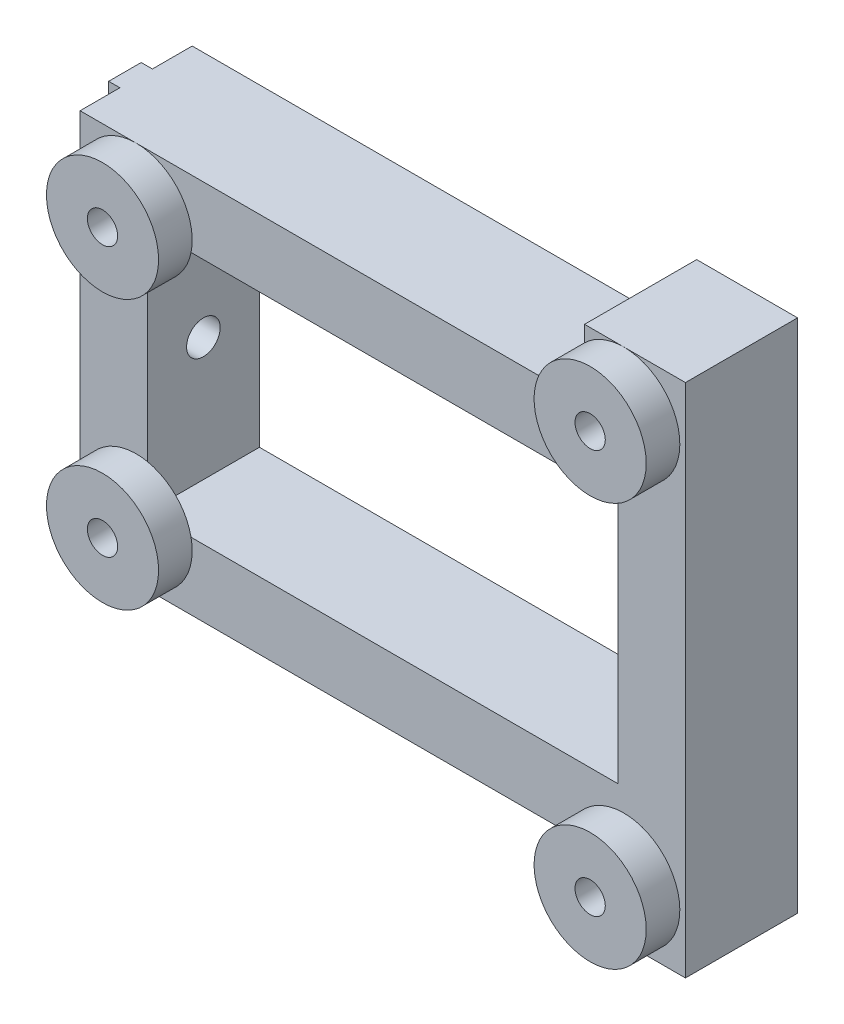
SolidWorks part; units mm, degrees
ref_plane "Plan de face" through (0, 0, 0) normal (0, 0, 1) x (1, 0, 0)
ref_plane "Plan de dessus" through (0, 0, 0) normal (0, 1, 0) x (1, 0, 0)
ref_plane "Plan de droite" through (0, 0, 0) normal (1, 0, 0) x (0, 0, -1)
sketch "Esquisse1" plane through (0, 0, 0) normal (0, 0, 1) x (1, 0, 0)
  line L1 (-27, -23) -> (27, -23)
  line L2 (-27, -23) -> (-27, 23)
  line L3 (-27, 23) -> (27, 23)
  line L4 (27, -23) -> (27, 23)
  point P7 (0, -23)
  point P8 (-27, 0)
  dimension "D1" = 46
  dimension "D2" = 54
extrude "Boss.-Extru.1" add sketch "Esquisse1" along normal blind 10
sketch "Esquisse2" plane through (0, 0, 10) normal (0, 0, 1) x (1, 0, 0)
  line L1 (-27, -23) -> (27, -23) construction
  line L2 (27, 23) -> (-27, 23) construction
  line L3 (-27, 23) -> (-27, -23) construction
  circle A0 centre (-22, -12) radius 1.35
  circle A1 centre (-22, 12) radius 1.35
  circle A2 centre (21.5, 18) radius 1.35
  circle A3 centre (21.5, -18) radius 1.35
  dimension "D1" = 2.7
  dimension "D2" = 48.5
  dimension "D3" = 5
  dimension "D4" = 11
  dimension "D5" = 11
  dimension "D6" = 5
  dimension "D7" = 5
  dimension "D8" = 24
  dimension "D9" = 36
extrude "Enlèv. mat.-Extru.1" cut sketch "Esquisse2" against normal through all
sketch "Esquisse3" plane through (0, 0, 10) normal (0, 0, 1) x (1, 0, 0)
  circle A0 centre (-22, 12) radius 5
  circle A1 centre (-22, -12) radius 5
  circle A2 centre (21.5, -18) radius 5
  circle A3 centre (21.5, 18) radius 5
  circle A4 centre (21.5, 18) radius 1.35 construction
  circle A5 centre (-22, 12) radius 1.35 construction
  circle A6 centre (-22, -12) radius 1.35 construction
  circle A7 centre (21.5, -18) radius 1.35 construction
  dimension "D1" = 10
extrude "Boss.-Extru.2" add sketch "Esquisse3" along normal blind 3
sketch "Esquisse4" plane through (0, -23, 0) normal (0, -1, 0) x (1, 0, 0)
  line L0 (-27, 10) -> (21.5, 10) construction
  line L1 (18, 10) -> (-27, 10)
  line L2 (18, 10) -> (18, 0)
  line L3 (18, 0) -> (-27, 0)
  line L4 (-27, 10) -> (-27, 0)
  dimension "D2" = 45
extrude "Enlèv. mat.-Extru.2" cut sketch "Esquisse4" against normal blind 6
sketch "Esquisse6" plane through (0, 23, 0) normal (0, 1, 0) x (1, 0, 0)
  line L0 (21.5, -10) -> (-27, -10) construction
  line L1 (-27, 0) -> (18, 0)
  line L2 (-27, 0) -> (-27, -10)
  line L3 (-27, -10) -> (18, -10)
  line L4 (18, 0) -> (18, -10)
  line L5 (-27, -10) -> (-27, 0) construction
  line L6 (27, 0) -> (-27, 0) construction
  line L7 (16.5, -10) -> (26.5, -10) construction
extrude "Enlèv. mat.-Extru.3" cut sketch "Esquisse6" against normal blind 6
sketch "Esquisse7" plane through (-27, 0, 0) normal (-1, 0, 0) x (0, 0, 1)
  line L1 (3.55, 17) -> (6.45, 17)
  line L2 (3.55, 17) -> (3.55, -17)
  line L3 (3.55, -17) -> (6.45, -17)
  line L4 (6.45, 17) -> (6.45, -17)
  line L9 (0, 17) -> (10, 17) construction
  line L10 (10, -17) -> (0, -17) construction
  point P4 (5, 17)
  point P10 (5, 17)
  dimension "D1" = 2.9
extrude "Boss.-Extru.3" add sketch "Esquisse7" along normal blind 1
sketch "Esquisse10" plane through (0, 0, 10) normal (0, 0, 1) x (1, 0, 0)
  line L0 (18, 17) -> (54.5, 17) construction
  line L1 (-21, 11) -> (21, 11)
  line L2 (-21, 11) -> (-21, -11)
  line L3 (-21, -11) -> (21, -11)
  line L4 (21, 11) -> (21, -11)
  line L5 (54.5, -17) -> (18, -17) construction
  line L6 (-27, -17) -> (-27, 17) construction
  line L7 (27, -23) -> (27, 23) construction
  dimension "D1" = 6
  dimension "D2" = 6
  dimension "D3" = 6
  dimension "D4" = 6
extrude "Enlèv. mat.-Extru.5" cut sketch "Esquisse10" against normal through all
sketch "Esquisse8" plane through (-28, 0, 0) normal (-1, 0, 0) x (0, 0, 1)
  line L0 (6.45, 17) -> (3.55, 17) construction
  line L2 (6.45, -17) -> (6.45, 17) construction
  circle A0 centre (5, 0) radius 1.5
  point P7 (5, 17)
  point P12 (6.45, 0)
  dimension "D1" = 3
extrude "Enlèv. mat.-Extru.4" cut sketch "Esquisse8" against normal up to next
sketch "Esquisse11" plane through (0, 0, 10) normal (0, 0, -1) x (-1, 0, 0)
  circle A0 centre (-21.5, 18) radius 1.35
  circle A1 centre (22, 12) radius 1.35
  circle A2 centre (22, -12) radius 1.35
  circle A3 centre (-21.5, -18) radius 1.35
  circle A4 centre (-21.5, -18) radius 1.35 construction
  circle A5 centre (-21.5, 18) radius 1.35 construction
  circle A6 centre (22, -12) radius 1.35 construction
  circle A7 centre (22, 12) radius 1.35 construction
extrude "Enlèv. mat.-Extru.6" cut sketch "Esquisse11" against normal through all
